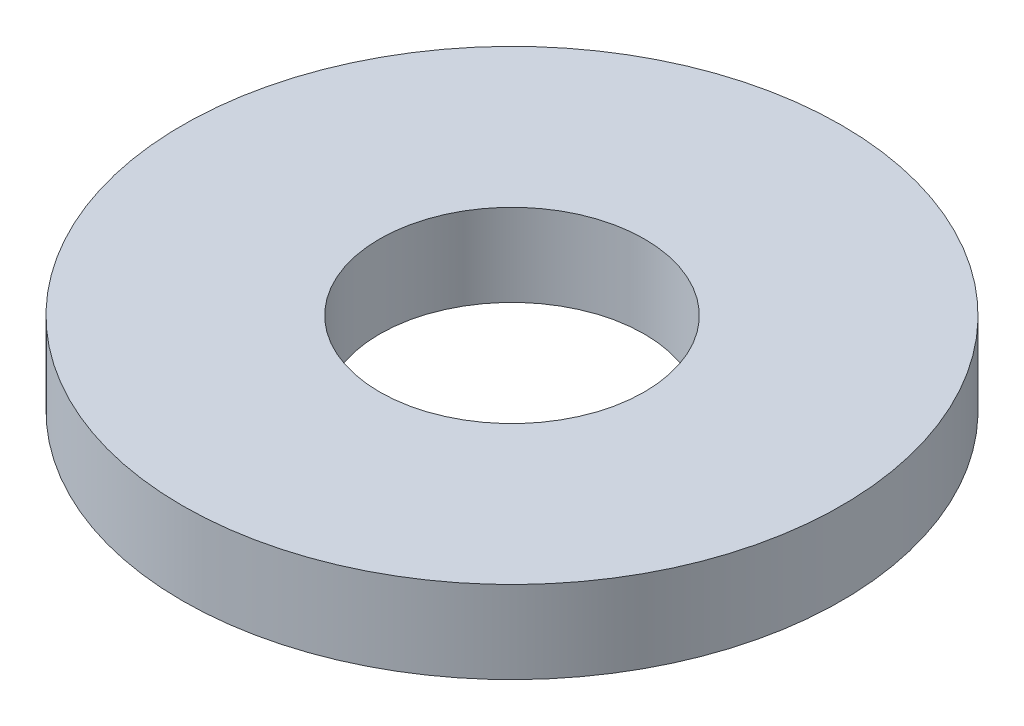
SolidWorks part; units mm, degrees
material "6061-T6 (SS)"
ref_plane "Front Plane" through (0, 0, 0) normal (0, 0, 1) x (1, 0, 0)
ref_plane "Top Plane" through (0, 0, 0) normal (0, 1, 0) x (1, 0, 0)
ref_plane "Right Plane" through (0, 0, 0) normal (1, 0, 0) x (0, 0, -1)
sketch "Sketch1" plane through (0, 0, 0) normal (0, 1, 0) x (1, 0, 0)
  circle A0 centre (0, 0) radius 2.5527
  circle A1 centre (0, 0) radius 6.35
  dimension "D1" = 5.1054
  dimension "D2" = 12.7
extrude "Boss-Extrude1" add sketch "Sketch1" along normal blind 1.5875
